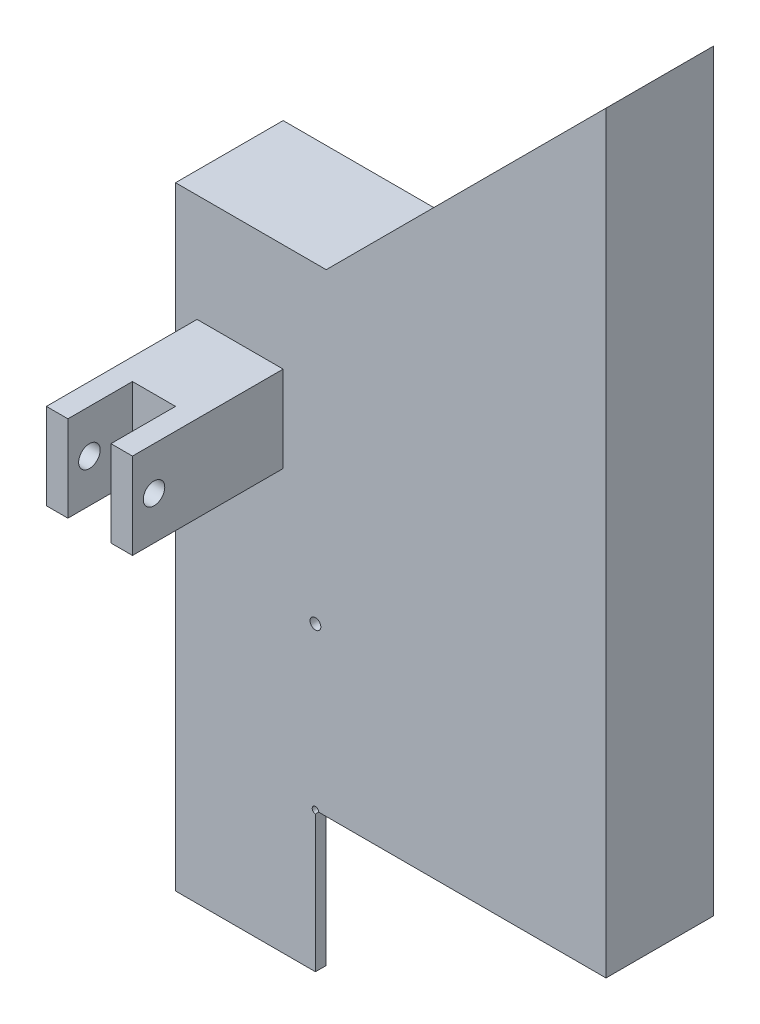
SolidWorks part; units mm, degrees
ref_plane "Přední rovina" through (0, 0, 0) normal (0, 0, 1) x (1, 0, 0)
ref_plane "Horní rovina" through (0, 0, 0) normal (0, 1, 0) x (1, 0, 0)
ref_plane "Pravá rovina" through (0, 0, 0) normal (1, 0, 0) x (0, 0, -1)
sketch "Skica1" plane through (0, 0, 0) normal (0, 0, 1) x (1, 0, 0)
  line L0 (0, 0) -> (200, 0)
  line L1 (200, 0) -> (200, 350)
  line L2 (200, 350) -> (70, 220)
  line L3 (70, 220) -> (0, 220)
  line L4 (0, 220) -> (0, 0)
  dimension "D1" = 350
  dimension "D2" = 200
  dimension "D3" = 70
  dimension "D4" = 220
extrude "Přidat vysunutím1" add sketch "Skica1" along normal blind 50
sketch "Skica2" plane through (0, 0, 0) normal (0, -1, 0) x (1, 0, 0)
  line L1 (0, 50) -> (130, 50)
  line L2 (0, 50) -> (0, 45)
  line L3 (0, 45) -> (130, 45)
  line L4 (130, 50) -> (130, 45)
  dimension "D1" = 130
  dimension "D2" = 5
extrude "Přidat vysunutím2" add sketch "Skica2" along normal blind 65
sketch "Skica3" plane through (0, 0, 50) normal (0, 0, 1) x (1, 0, 0)
  line L1 (130, -65) -> (65, -65)
  line L2 (130, -65) -> (130, 0)
  line L3 (130, 0) -> (65, 0)
  line L4 (65, -65) -> (65, 0)
  dimension "D1" = 65
  dimension "D2" = 65
extrude "Odebrat vysunutím1" cut sketch "Skica3" against normal blind 5
sketch "Skica4" plane through (0, 0, 50) normal (0, 0, 1) x (1, 0, 0)
  line L0 (70, 220) -> (0, 220) construction
  line L1 (10, 170) -> (50, 170)
  line L2 (10, 170) -> (10, 130)
  line L3 (10, 130) -> (50, 130)
  line L4 (50, 170) -> (50, 130)
  line L5 (0, 220) -> (0, -65) construction
  dimension "D1" = 40
  dimension "D2" = 40
  dimension "D3" = 50
  dimension "D4" = 10
extrude "Přidat vysunutím3" add sketch "Skica4" along normal blind 40
sketch "Skica5" plane through (0, 0, 90) normal (0, 0, 1) x (1, 0, 0)
  line L0 (10, 130) -> (50, 130) construction
  line L1 (10, 170) -> (20, 170)
  line L2 (10, 170) -> (10, 130)
  line L3 (10, 130) -> (20, 130)
  line L4 (20, 170) -> (20, 130)
  line L6 (50, 170) -> (40, 170)
  line L7 (50, 170) -> (50, 130)
  line L8 (50, 130) -> (40, 130)
  line L9 (40, 170) -> (40, 130)
  dimension "D1" = 10
  dimension "D2" = 10
extrude "Přidat vysunutím4" add sketch "Skica5" along normal blind 30
sketch "Skica6" plane through (50, 0, 0) normal (1, 0, 0) x (0, 0, -1)
  line L0 (-120, 130) -> (-50, 130) construction
  line L1 (-120, 130) -> (-120, 170) construction
  circle A0 centre (-110, 150) radius 5
  dimension "D1" = 10
  dimension "D2" = 20
  dimension "D3" = 10
extrude "Odebrat vysunutím2" cut sketch "Skica6" against normal blind 40
sketch "Skica7" plane through (0, 0, 50) normal (0, 0, 1) x (1, 0, 0)
  line L0 (65, -65) -> (0, -65) construction
  line L1 (0, 220) -> (0, -65) construction
  circle A0 centre (65, 75) radius 2.5
  dimension "D1" = 5
  dimension "D2" = 140
  dimension "D3" = 65
extrude "Odebrat vysunutím3" cut sketch "Skica7" against normal blind 55
sketch "Skica8" plane through (0, 0, 50) normal (0, 0, 1) x (1, 0, 0)
  line L0 (0, 220) -> (0, -65) construction
  line L1 (65, -65) -> (0, -65) construction
  circle A0 centre (65, 0) radius 1.5
  dimension "D1" = 3
  dimension "D2" = 65
  dimension "D3" = 65
extrude "Odebrat vysunutím4" cut sketch "Skica8" against normal blind 50
sketch "Skica9" plane through (0, 0, 50) normal (0, 0, 1) x (1, 0, 0)
  line L1 (63.5, 0) -> (-2.8275, 0)
  line L2 (63.5, 0) -> (63.5, -68.4972)
  line L3 (63.5, -68.4972) -> (-2.8275, -68.4972)
  line L4 (-2.8275, 0) -> (-2.8275, -68.4972)
